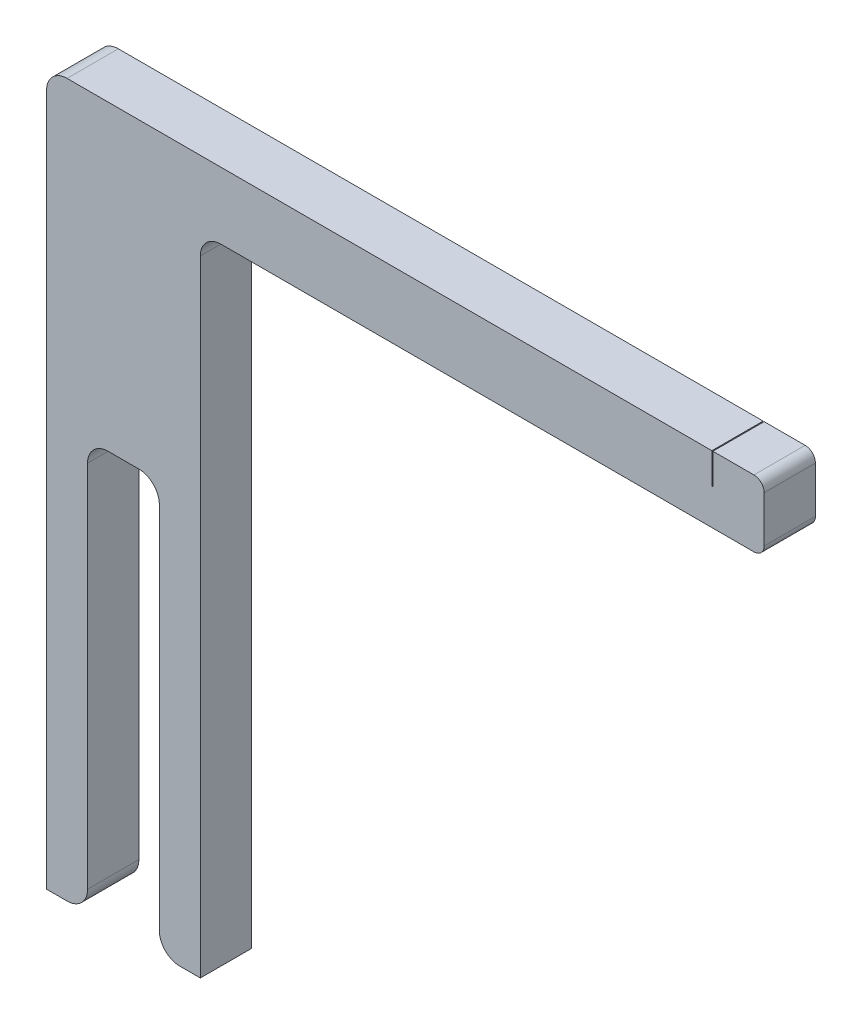
SolidWorks part; units mm, degrees
ref_plane "Front Plane" through (0, 0, 0) normal (0, 0, 1) x (1, 0, 0)
ref_plane "Top Plane" through (0, 0, 0) normal (0, 1, 0) x (1, 0, 0)
ref_plane "Right Plane" through (0, 0, 0) normal (1, 0, 0) x (0, 0, -1)
sketch "Sketch1" plane through (0, 0, 0) normal (0, 0, 1) x (1, 0, 0)
  line L0 (0, 0) -> (0, 67.5)
  line L1 (2, 69.5) -> (69, 69.5)
  line L2 (70, 68.5) -> (70, 64)
  line L3 (69, 63) -> (17, 63)
  line L4 (15, 61) -> (15, 0)
  line L5 (15, 0) -> (11, 0)
  line L6 (4, 0) -> (4, 40)
  line L7 (4, 40) -> (11, 40)
  line L8 (11, 40) -> (11, 0)
  line L9 (4, 0) -> (0, 0)
  arc A0 (17, 63) -> (15, 61) centre (17, 61) ccw
  arc A1 (2, 69.5) -> (0, 67.5) centre (2, 67.5) ccw
  arc A2 (70, 68.5) -> (69, 69.5) centre (69, 68.5) ccw
  arc A3 (69, 63) -> (70, 64) centre (69, 64) ccw
  point P11 (0, 69.5)
  point P14 (70, 69.5)
  point P17 (70, 63)
  dimension "D5" = 2
  dimension "D6" = 2
  dimension "D7" = 1
  dimension "D2" = 15
  dimension "D3" = 6.5
  dimension "D4" = 70
  dimension "D8" = 4
  dimension "D9" = 4
  dimension "D10" = 40
extrude "Boss-Extrude1" add sketch "Sketch1" along normal blind 5
sketch "Sketch3" plane through (0, 69.5, 0) normal (0, 1, 0) x (1, 0, 0)
  line L0 (0, -2.5) -> (64.95, -2.5) construction
  line L1 (0, -5) -> (0, 0) construction
  line L2 (69, 0) -> (2, 0) construction
  line L3 (64.9, -5) -> (65, -5)
  line L4 (64.9, -5) -> (64.9, 0)
  line L5 (64.9, 0) -> (65, 0)
  line L6 (65, -5) -> (65, 0)
  line L7 (64.9, -5) -> (65, 0) construction
  line L8 (64.9, 0) -> (65, -5) construction
  dimension "D1" = 64.95
extrude "Cut-Extrude1" cut sketch "Sketch3" against normal blind 3
fillet "Fillet1" radius 2 4 edges at (11, 0, 2.5) (4, 0, 2.5) (11, 40, 2.5) (4, 40, 2.5)
equation "\"A.L\"= 0.07m"
equation "\"A.h\"= 0.007m"
equation "\"A.d\"= 0.005m"
equation "\"A.delta\"= 45.0001"
equation "\"A.w\"= 0m"
equation "\"A.v\"= 0.013m"
equation "\"A.s\"= 0.014m"
equation "\"A.t\"= 0.007m"
equation "\"B.L\"= 0.065m"
equation "\"B.h\"= 0.008m"
equation "\"B.s\"= 0.016m"
equation "\"B.t\"= 0.008m"
equation "\"C.h\"= 0.0065m"
equation "\"C.d\"= 0.005m"
equation "\"C.L\"= 0.05m"
equation "\"C.wmax\"= 0.003m"
equation "\"D.L\"= 0.06m"
equation "\"D.h\"= 0.008m"
equation "\"D.s\"= 0.012m"
equation "\"D.t\"= 0.008m"
equation "\"a_h\"= 0.0001m"
equation "\"a_d\"= 0.005m"
equation "\"a_L\"= 0.008m"
equation "\"b_h\"= 0.0004m"
equation "\"b_d\"= 0.005m"
equation "\"b_L\"= 0.007m"
equation "\"c_h\"= 0.0001m"
equation "\"c_d\"= 0.005m"
equation "\"c_L\"= 0.01m"
equation "\"d_h\"= 0.0001m"
equation "\"d_d\"= 0.005m"
equation "\"d_L\"= 0.01m"
equation "\"S.h\"= 0.015m"
equation "\"S.L\"= 0.09275m"
equation "\"D1@Sketch1\"=\"C.h\"+\"C.wmax\"+60mm"
equation "\"D2@Sketch1\"=\"S.h\""
equation "\"D3@Sketch1\"=\"C.h\""
equation "\"D4@Sketch1\"=\"C.L\"+\"S.h\"+0.005"
equation "\"D1@Boss-Extrude1\"=0.005m"
equation "\"D1@Sketch3\"=\"C.L\"+\"S.h\"-\"c_h\"/2"
equation "\"D2@Sketch3\"=\"c_h\""
